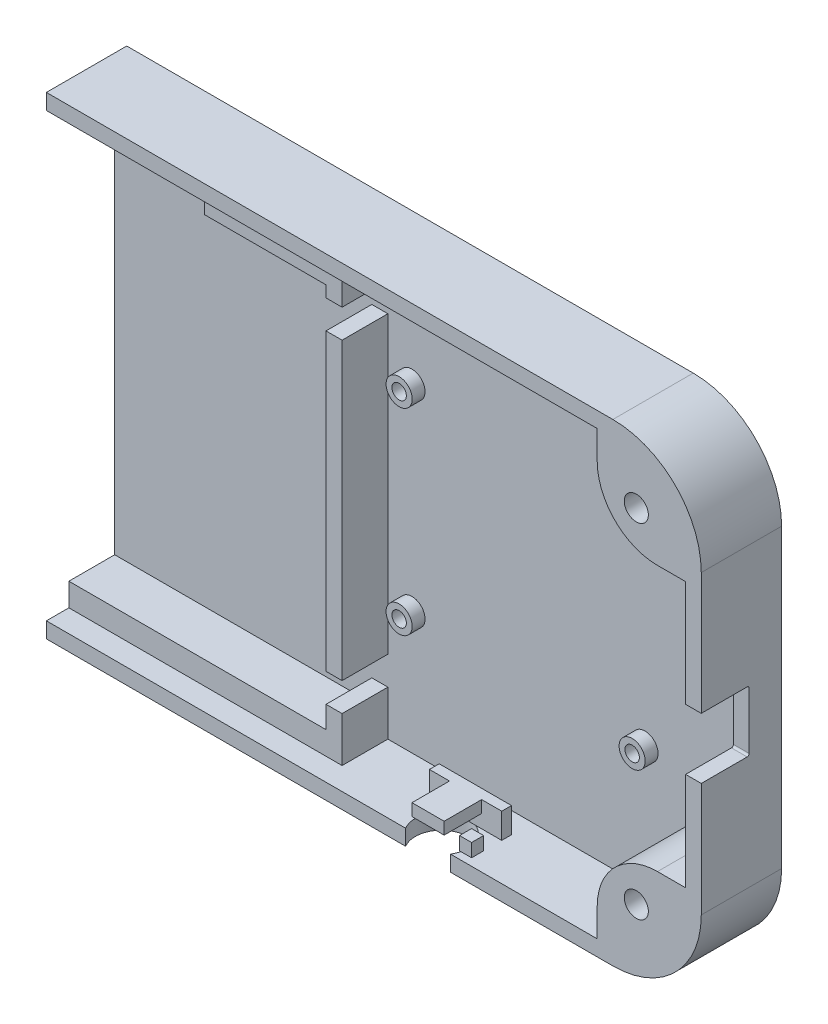
SolidWorks part; units mm, degrees
note: The reader was unsure of these and kept them because the rebuilt part matched: shared geometry of "Sketch1<3>", "Sketch6<2>", "Sketch11<3>", "Sketch12<3>".
ref_plane "Front Plane" through (0, 0, 0) normal (0, 0, 1) x (1, 0, 0)
ref_plane "Top Plane" through (0, 0, 0) normal (0, 1, 0) x (1, 0, 0)
ref_plane "Right Plane" through (0, 0, 0) normal (1, 0, 0) x (0, 0, -1)
sketch "Sketch1" plane through (0, 0, 0) normal (0, 0, 1) x (1, 0, 0)
  line L0 (0, 55) -> (0, 58.9) construction
  line L1 (163, 58.9) -> (-163, 58.9)
  line L2 (163, 58.9) -> (163, -58.9)
  line L3 (163, -58.9) -> (-163, -58.9)
  line L4 (-163, 58.9) -> (-163, -58.9)
  line L5 (163, 58.9) -> (-163, -58.9) construction
  line L6 (163, -58.9) -> (-163, 58.9) construction
  line L7 (-159.1, -55) -> (159.1, -55)
  line L8 (-159.1, -55) -> (-159.1, 55)
  line L9 (-159.1, 55) -> (159.1, 55)
  line L10 (159.1, -55) -> (159.1, 55)
  line L11 (-159.1, -55) -> (159.1, 55) construction
  line L12 (-159.1, 55) -> (159.1, -55) construction
  line L13 (-159.1, 0) -> (-163, 0) construction
  line L14 (159.1, 4.25) -> (159.1, -6.25) construction
  point P0 (0, 0)
  point P6 (0, 0)
  dimension "D1" = 3.9
  dimension "D2" = 110
extrude "Boss-Extrude1" add sketch "Sketch1" along normal blind 20 contours L1 L4 L3 L2 L10 L7 L8 L9
extrude "Boss-Extrude2" add sketch "Sketch1<3>" along normal blind 3 contours L7 L10 L9 L8
sketch "Sketch1<3>" plane through (0, 0, 0) normal (0, 0, 1) x (1, 0, 0) same geometry as "Sketch1"
sketch "Sketch5" plane through (0, 0, 0) normal (0, 0, 1) x (1, 0, 0)
  line L0 (64, 55) -> (64, 43.7953)
  line L1 (-159.1, 55) -> (159.1, 55) construction
  line L2 (-159.1, -55) -> (159.1, -55) construction
  line L3 (64, -55) -> (68, -55)
  line L4 (68, -55) -> (68, -43.7953)
  line L5 (68, 55) -> (64, 55)
  line L6 (68, -36.6942) -> (64, -36.6942)
  line L7 (-99, -43.7953) -> (-103, -43.7953)
  line L8 (-103, -43.7953) -> (-103, 55)
  line L9 (-103, 55) -> (-99, 55)
  line L10 (-99, 55) -> (-99, -43.7953)
  line L12 (64, -49.2598) -> (-83.5893, -49.2598)
  line L13 (68, 43.7953) -> (68, 55)
  line L14 (64, -43.7953) -> (68, -43.7953)
  line L15 (64, 36.6942) -> (68, 36.6942)
  line L16 (64, 43.7953) -> (68, 43.7953)
  line L17 (68, -36.6942) -> (68, 36.6942)
  line L18 (64, -43.7953) -> (64, -55)
  line L19 (64, 36.6942) -> (64, -36.6942)
  line L20 (0, 0) -> (61.1826, 0) construction
  line L21 (163, 58.9) -> (163, -58.9) construction
  line L22 (-83.5893, -49.2598) -> (-83.5893, -55)
  line L23 (-137.1, -55) -> (-67.7766, -55) construction
  line L24 (-83.5893, -55) -> (64, -55)
  line L25 (-99, 43.7953) -> (-34.5955, 43.7953)
  line L26 (-34.5955, 43.7953) -> (-34.5955, 55)
  line L27 (-137.1, 55) -> (-24, 55) construction
  line L28 (-34.5955, 55) -> (-99, 55)
  line L29 (64, 46.6245) -> (33.7813, 46.6245)
  line L31 (33.7813, 46.6245) -> (33.7813, 55)
  line L32 (24, 55) -> (137.1, 55) construction
  line L33 (33.7813, 55) -> (64, 55)
  dimension "D1" = 4
  dimension "D2" = 163
  dimension "D3" = 99
sketch "Sketch6" plane through (0, 0, 0) normal (0, 0, 1) x (1, 0, 0)
  line L1 (-163, 0) -> (159.1, 0) construction
  line L2 (-163, 58.9) -> (-163, -58.9) construction
  line L3 (159.1, -55) -> (159.1, 55) construction
  circle A11 centre (132, -24.5) radius 1.8
  circle A12 centre (132, -24.5) radius 3.25
  circle A13 centre (74, -24.5) radius 1.8
  circle A14 centre (74, -24.5) radius 3.25
  circle A15 centre (74, 24.5) radius 1.8
  circle A17 centre (74, 24.5) radius 3.25
  circle A18 centre (132, 24.5) radius 1.8
  circle A19 centre (132, 24.5) radius 3.25
  dimension "D1" = 3.6
  dimension "D2" = 6.5
extrude "Boss-Extrude6" add sketch "Sketch6" along normal blind 3.2 from surface at 3 starting at face at (0, 0, 3)
fillet "Fillet1" radius 22 8 edges at (163, -58.9, 10) (163, 58.9, 10) (-163, -58.9, 10) (-163, 58.9, 10) (159.1, -55, 11.5) (159.1, 55, 11.5) (-159.1, -55, 11.5) (-159.1, 55, 11.5)
sketch "Sketch9" plane through (0, 0, 0) normal (1, 0, 0) x (0, 0, -1)
  line L0 (-20, -8.55) -> (-8.58, -8.55)
  line L2 (-20, -33) -> (-20, 33) construction
  line L3 (-8.08, -8.05) -> (-8.08, 6.05)
  line L4 (-8.58, 6.55) -> (-20, 6.55)
  line L6 (-20, 6.55) -> (-20, -8.55)
  line L9 (-22.5, -3.9) -> (-22.5, 1.9) construction
  line L10 (-8.08, -1) -> (-22.5, -1) construction
  line L11 (-17.28, 5.25) -> (-18.44, 5.25) construction
  line L13 (-9.38, -6.55) -> (-9.38, -1.01) construction
  arc A0 (-8.08, 6.05) -> (-8.58, 6.55) centre (-8.58, 6.05) ccw
  arc A1 (-8.58, -8.55) -> (-8.08, -8.05) centre (-8.58, -8.05) ccw
  dimension "D2" = 0.5
  dimension "D1" = 1.3
  dimension "D3" = 1.3
extrude "Cut-Extrude3" cut sketch "Sketch9" against normal up to surface (3.9 mm away) from surface at 163 up to face at (159.1, 0, 11.5) starting at face at (163, 0, 10)
extrude "Cut-Extrude4" cut sketch "Sketch6<2>" against normal blind 1.8 from surface at 3 contours A11 | A18 | A15 | A13 starting at face at (135.25, 24.5, 3)
sketch "Sketch6<2>" plane through (0, 0, 0) normal (0, 0, 1) x (1, 0, 0) same geometry as "Sketch6"
extrude "Boss-Extrude7" add sketch "Sketch5" along normal blind 14.4
sketch "Sketch10" plane through (0, 0, 0) normal (0, 1, 0) x (1, 0, 0)
  line L0 (-163, -16.6656) -> (163, -16.6656) construction
  line L1 (0, 0) -> (0, -20) construction
  line L2 (141, -20) -> (-141, -20) construction
  line L3 (163, -20) -> (163, 0) construction
  line L4 (-163, 0) -> (-163, -20) construction
  line L5 (141, 0) -> (-141, 0) construction
  circle A0 centre (95, -16.6656) radius 6.5
  circle A1 centre (-95, -16.6656) radius 6.5
  dimension "D2" = 13
  dimension "D1" = 95
  dimension "D3" = 16.6656
extrude "Cut-Extrude5" cut sketch "Sketch10" against normal up to surface (3.9 mm away) from surface
sketch "Sketch11" plane through (0, 0, 0) normal (0, 1, 0) x (1, 0, 0)
  line L0 (91, -8.2356) -> (99, -8.2356)
  line L1 (99, -10.6656) -> (99, -20)
  line L2 (99, -20) -> (91, -20)
  line L3 (91, -20) -> (91, -10.6656)
  line L4 (95, -16.6656) -> (95, -8.2356) construction
  line L5 (104, -10.6656) -> (86, -10.6656)
  line L6 (86, -10.6656) -> (86, -8.2356)
  line L7 (86, -8.2356) -> (104, -8.2356)
  line L8 (104, -8.2356) -> (104, -10.6656)
  line L9 (-89.4204, -20) -> (89.4204, -20) construction
  line L10 (104, -15.1656) -> (101, -15.1656)
  line L11 (101, -11.6656) -> (101, -21.6656) construction
  line L12 (101, -15.1656) -> (101, -18.1656)
  line L13 (101, -18.1656) -> (104, -18.1656)
  line L14 (104, -18.1656) -> (104, -15.1656)
  line L15 (95, -16.6656) -> (104, -16.6656) construction
  line L17 (101.35, -19.1656) -> (102.05, -19.1656) construction
  line L18 (0, 0) -> (-0.0266, -23.6313) construction
  line L19 (-60.5266, -23.6313) -> (60.4734, -23.6313) construction
  line L20 (-86.0238, -10.4716) -> (-86.0184, -8.0417)
  line L21 (-99.0449, -19.7767) -> (-91.0449, -19.7947)
  line L22 (-91.0449, -19.7947) -> (-91.0238, -10.4604)
  line L23 (-101.0339, -14.9378) -> (-101.0407, -17.9378)
  line L24 (-101.0407, -17.9378) -> (-104.0407, -17.931)
  line L25 (-104.0407, -17.931) -> (-104.0339, -14.931)
  line L26 (-104.0339, -14.931) -> (-101.0339, -14.9378)
  line L27 (-99.0238, -10.4423) -> (-99.0449, -19.7767)
  line L28 (-86.0184, -8.0417) -> (-104.0183, -8.0011)
  line L29 (-104.0238, -10.431) -> (-86.0238, -10.4716)
  line L30 (-104.0183, -8.0011) -> (-104.0238, -10.431)
  dimension "D1" = 8
  dimension "D2" = 18
  dimension "D3" = 1
  dimension "D4" = 6
extrude "Boss-Extrude8" add sketch "Sketch11" along normal blind 3.3 from surface at -55 contours L26 L25 L24 L23 | L28 L30 L29 L20 | L5 L6 L7 L8 | L13 L14 L10 L12 starting at face at (-2.5982, -55, 11.7609)
extrude "Boss-Extrude9" add sketch "Sketch11<3>" along normal blind 3 from surface at -51.7 contours L29 L27 L21 L22 | L1 L5 L3 L2 | L8 L7 L0 L6 L5
sketch "Sketch11<3>" plane through (0, 0, 0) normal (0, 1, 0) x (1, 0, 0) same geometry as "Sketch11"
sketch "Sketch12" plane through (0, 0, 0) normal (0, 0, 1) x (1, 0, 0)
  line L0 (0, 0) -> (0, -50000) construction
  line L1 (-163, 0) -> (163.7106, 0) construction
  line L10 (-137.1, -55) -> (-137.1, -48)
  line L11 (-152.1, -33) -> (-159.1, -33)
  line L12 (-137.1, -33) -> (-156.5563, -52.4563) construction
  line L13 (-163, 36.9) -> (-163, -36.9) construction
  line L14 (-137.1, -33) -> (-137.1, -55)
  line L15 (-159.1, -33) -> (-137.1, -33)
  line L16 (-137.1, 33) -> (-156.5563, 52.4563) construction
  line L17 (-159.1, 33) -> (-152.1, 33)
  line L18 (-137.1, 48) -> (-137.1, 55)
  line L19 (-137.1, 33) -> (-159.1, 33)
  line L20 (-137.1, 55) -> (-137.1, 33)
  line L21 (137.1, 33) -> (156.5563, 52.4563) construction
  line L22 (137.1, -33) -> (156.5563, -52.4563) construction
  line L23 (163, 0) -> (-163.7106, 0) construction
  line L24 (137.1, 55) -> (137.1, 48)
  line L25 (152.1, 33) -> (159.1, 33)
  line L26 (137.1, 33) -> (137.1, 55)
  line L27 (159.1, 33) -> (137.1, 33)
  line L28 (159.1, -33) -> (152.1, -33)
  line L29 (137.1, -48) -> (137.1, -55)
  line L30 (137.1, -33) -> (159.1, -33)
  line L31 (137.1, -55) -> (137.1, -33)
  circle A0 centre (-146.8282, -42.7282) radius 3
  arc A2 (-137.1, -55) -> (-159.1, -33) centre (-137.1, -33) cw
  arc A3 (-163, -36.9) -> (-141, -58.9) centre (-141, -36.9) ccw construction
  arc A4 (-137.1, 55) -> (-159.1, 33) centre (-137.1, 33) ccw
  circle A5 centre (-146.8282, 42.7282) radius 3
  circle A6 centre (146.8282, 42.7282) radius 3
  arc A7 (137.1, 55) -> (159.1, 33) centre (137.1, 33) cw
  arc A8 (137.1, -55) -> (159.1, -33) centre (137.1, -33) ccw
  circle A9 centre (146.8282, -42.7282) radius 3
  arc A10 (152.1, 33) -> (137.1, 48) centre (152.1, 48) cw
  arc A11 (-137.1, 48) -> (-152.1, 33) centre (-152.1, 48) cw
  arc A12 (-137.1, -48) -> (-152.1, -33) centre (-152.1, -48) ccw
  arc A13 (137.1, -48) -> (152.1, -33) centre (152.1, -48) cw
  dimension "D1" = 6
  dimension "D2" = 15
extrude "Boss-Extrude10" add sketch "Sketch12" against normal up to surface (17 mm away) from surface contours L10 A12 L11 A2 A0 | A11 L18 A4 L17 A5 | A10 L25 A7 L24 A6 | A13 L29 A8 L28 A9
extrude "Cut-Extrude6" cut sketch "Sketch12<3>" along normal blind 6 from surface at 0 contours A6 | A9 | A0 | A5 starting at face at (0, 0, 0)
sketch "Sketch12<3>" plane through (0, 0, 0) normal (0, 0, 1) x (1, 0, 0) same geometry as "Sketch12"
sketch "Sketch13" plane through (0, 0, 0) normal (0, 0, 1) x (1, 0, 0)
  circle A0 centre (-146.8282, -42.7282) radius 4.5
  circle A1 centre (-146.8282, 42.7282) radius 4.5
  circle A2 centre (146.8282, 42.7282) radius 4.5
  circle A3 centre (146.8282, -42.7282) radius 4.5
  dimension "D1" = 9
extrude "Cut-Extrude7" cut sketch "Sketch13" along normal blind 4 from surface at 0 starting at face at (-143.8282, 42.7282, 0)
sketch "Sketch14" plane through (0, 0, 0) normal (0, 0, 1) x (1, 0, 0)
  line L0 (0, 62.7144) -> (0, -69.5517)
  line L1 (0, -69.5517) -> (-179.9414, -69.5517)
  line L2 (-179.9414, -69.5517) -> (-179.9414, 62.7144)
  line L3 (-179.9414, 62.7144) -> (0, 62.7144)
extrude "Cut-Extrude8" cut sketch "Sketch14" against normal blind 40 and the other way blind 30
